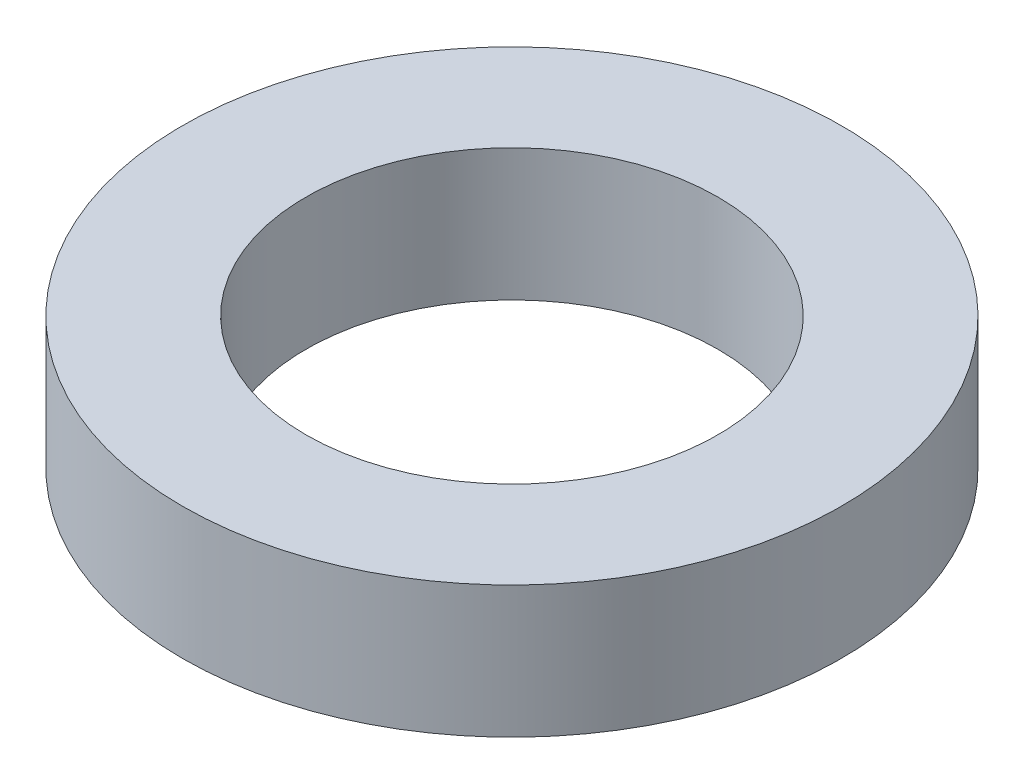
SolidWorks part; units mm, degrees
ref_plane "Front Plane" through (0, 0, 0) normal (0, 0, 1) x (1, 0, 0)
ref_plane "Top Plane" through (0, 0, 0) normal (0, 1, 0) x (1, 0, 0)
ref_plane "Right Plane" through (0, 0, 0) normal (1, 0, 0) x (0, 0, -1)
sketch "Sketch1" plane through (0, 0, 0) normal (0, 1, 0) x (1, 0, 0)
  circle A0 centre (0, 0) radius 60
  dimension "FLANGE_OD" = 120
extrude "Boss-Extrude1" add sketch "Sketch1" along normal blind 24
sketch "Sketch2" plane through (0, 0, 0) normal (0, 1, 0) x (1, 0, 0)
  circle A0 centre (0, 0) radius 37.5
  dimension "BORE_D" = 75
extrude "Cut-Extrude1" cut sketch "Sketch2" along normal through all
sketch "Sketch3" plane through (0, 24, 0) normal (0, 1, 0) x (1, 0, 0)
  circle A0 centre (0, 0) radius 27.6313 construction
  circle A1 centre (-27.6313, 0) radius 3.0341
  dimension "BOLT_D" = 6.0683
  dimension "BOLT_PCD" = 55.2626
extrude "Cut-Extrude2" cut sketch "Sketch3" against normal blind 17.7869 rebuild error yes
pattern_circular "CirPattern1" count 4 over 360 rebuild error yes
